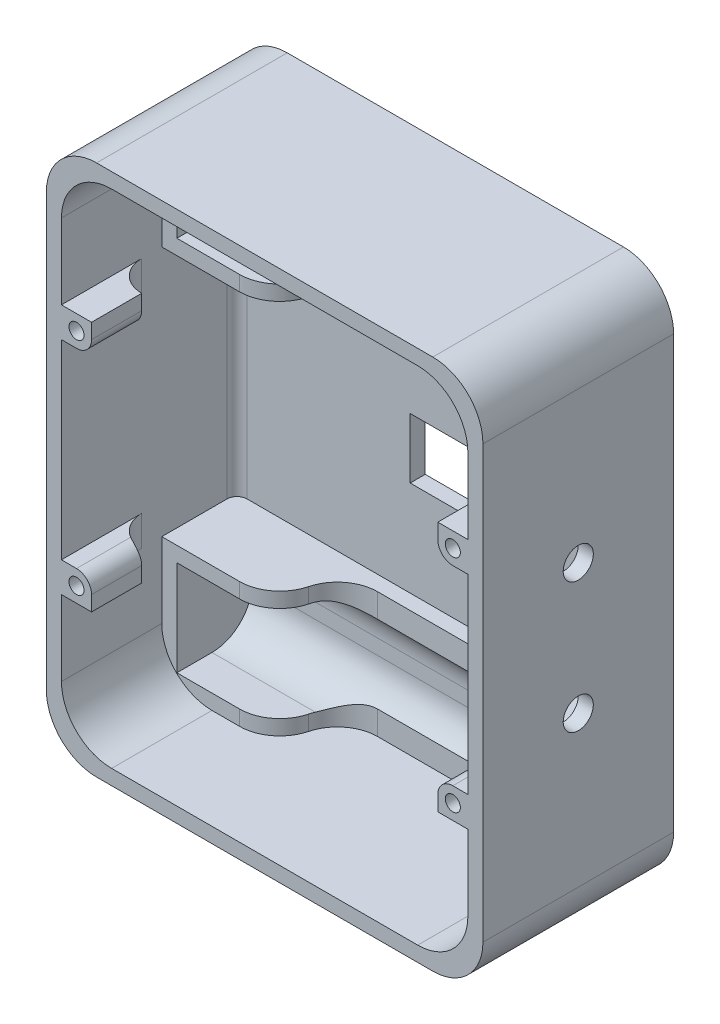
SolidWorks part; units mm, degrees
ref_plane "Front Plane" through (0, 0, 0) normal (0, 0, 1) x (1, 0, 0)
ref_plane "Top Plane" through (0, 0, 0) normal (0, 1, 0) x (1, 0, 0)
ref_plane "Right Plane" through (0, 0, 0) normal (1, 0, 0) x (0, 0, -1)
sketch "Sketch1" plane through (0, 0, 0) normal (0, 0, 1) x (1, 0, 0)
  line L0 (-3, -3) -> (78, -3)
  line L1 (0, 0) -> (75, 0)
  line L2 (0, 0) -> (0, 19)
  line L3 (0, 19) -> (75, 19)
  line L4 (75, 0) -> (75, 19)
  line L5 (78, -3) -> (78, 22)
  line L6 (-3, 22) -> (78, 22)
  line L7 (-3, -3) -> (-3, 22)
  dimension "D1" = 19
  dimension "D2" = 75
  dimension "D3" = 3
extrude "Boss-Extrude1" add sketch "Sketch1" along normal blind 18
sketch "Sketch2" plane through (0, 0, 18) normal (0, 0, 1) x (1, 0, 0)
  line L0 (75, 0) -> (75, 19) construction
  line L1 (20, 29.533) -> (55, 29.533)
  line L2 (20, 29.533) -> (20, -14.7246)
  line L3 (20, -14.7246) -> (55, -14.7246)
  line L4 (55, 29.533) -> (55, -14.7246)
  line L5 (0, 19) -> (0, 0) construction
  dimension "D1" = 20
  dimension "D2" = 20
extrude "Cut-Extrude1" cut sketch "Sketch2" against normal blind 12
sketch "Sketch3" plane through (0, 0, 0) normal (0, 0, -1) x (-1, 0, 0)
  line L1 (3, -3) -> (-78, -3)
  line L2 (3, -3) -> (3, 22)
  line L3 (3, 22) -> (-78, 22)
  line L4 (-78, -3) -> (-78, 22)
extrude "Boss-Extrude2" add sketch "Sketch3" against normal blind 3
fillet "Fillet1" radius 8 2 edges at (37.5, 0, 3) (37.5, 19, 3)
fillet "Fillet2" radius 8 4 edges at (55, 19.6225, 6) (55, -0.6225, 6) (20, -0.6225, 6) (20, 19.6225, 6)
fillet "Fillet3" radius 8 4 edges at (55, 20.5, 18) (20, 20.5, 18) (55, -1.5, 18) (20, -1.5, 18)
sketch "Sketch4" plane through (0, -3, 0) normal (0, -1, 0) x (1, 0, 0)
  line L1 (-3, 0) -> (-33, 0)
  line L2 (-3, 0) -> (-3, 3)
  line L3 (-3, 3) -> (-33, 3)
  line L4 (-33, 0) -> (-33, 3)
  dimension "D1" = 30
  dimension "D2" = 3
extrude "Boss-Extrude3" add sketch "Sketch4" against normal up to surface (25 mm away) up to face at (37.5, 22, 10.8)
sketch "Sketch5" plane through (0, -3, 0) normal (0, -1, 0) x (1, 0, 0)
  line L1 (-3, 3) -> (78, 3)
  line L2 (-3, 3) -> (-3, 0)
  line L3 (-3, 0) -> (78, 0)
  line L4 (78, 3) -> (78, 0)
extrude "Boss-Extrude4" add sketch "Sketch5" along normal blind 25
mirror "Mirror1" about plane through (0, -28, 0) normal (0, -1, 0) of bodies 105
sketch "Sketch6" plane through (0, 0, 3) normal (0, 0, 1) x (1, 0, 0)
  line L0 (-6, -81) -> (-6, 25)
  line L1 (-3, -78) -> (78, -78)
  line L2 (-3, -78) -> (-3, 22)
  line L3 (-3, 22) -> (78, 22)
  line L4 (78, -78) -> (78, 22)
  line L5 (-6, 25) -> (81, 25)
  line L6 (81, -81) -> (81, 25)
  line L7 (-6, -81) -> (81, -81)
  dimension "D1" = 3
extrude "Boss-Extrude6" add sketch "Sketch6" along normal blind 35 and the other way blind 3
sketch "Sketch7" plane through (0, 0, 3) normal (0, 0, 1) x (1, 0, 0)
  line L1 (-6, -81) -> (-52.2418, -81)
  line L2 (-6, -81) -> (-6, 49.2118)
  line L3 (-6, 49.2118) -> (-52.2418, 49.2118)
  line L4 (-52.2418, -81) -> (-52.2418, 49.2118)
extrude "Cut-Extrude2" cut sketch "Sketch7" against normal blind 35
sketch "Sketch8" plane through (0, 0, 3) normal (0, 0, 1) x (1, 0, 0)
  line L0 (-3, 22) -> (-3, -78) construction
  line L1 (31.5, -34) -> (43.5, -34)
  line L2 (31.5, -34) -> (31.5, -22)
  line L3 (31.5, -22) -> (43.5, -22)
  line L4 (43.5, -34) -> (43.5, -22)
  line L5 (28, -73.245) -> (47, -73.245) construction
  point P4 (31.5, -28)
  point P7 (-3, -28)
  point P8 (37.5, -34)
  point P11 (37.5, -73.245)
  dimension "D1" = 12
  dimension "D2" = 12
extrude "Cut-Extrude3" cut sketch "Sketch8" against normal blind 35
sketch "Sketch10" plane through (81, 0, 0) normal (1, 0, 0) x (0, 0, -1)
  line L0 (0, -81) -> (-38, -81) construction
  line L1 (0, 25) -> (-38, 25) construction
  circle A0 centre (-19, -41) radius 3
  circle A1 centre (-19, -15) radius 3
  point P7 (-19, -81)
  point P11 (-19, 25)
  dimension "D1" = 6
  dimension "D2" = 6
  dimension "D3" = 40
  dimension "D4" = 40
extrude "Cut-Extrude4" cut sketch "Sketch10" against normal blind 12
sketch "Sketch11" plane through (0, 0, 38) normal (0, 0, 1) x (1, 0, 0)
  line L0 (-3, -53) -> (-3, -3) construction
  line L1 (-3, -9) -> (0, -9)
  line L2 (-3, -9) -> (-3, -3)
  line L3 (-3, -3) -> (3, -3)
  line L4 (3, -6) -> (3, -3)
  line L6 (-3, -3) -> (12.5081, -3) construction
  line L11 (3, -50) -> (3, -53)
  line L12 (-3, -53) -> (3, -53)
  line L13 (-3, -47) -> (-3, -53)
  line L14 (-3, -47) -> (0, -47)
  line L15 (78, -47) -> (75, -47)
  line L16 (78, -47) -> (78, -53)
  line L17 (78, -53) -> (72, -53)
  line L18 (72, -50) -> (72, -53)
  line L19 (72, -6) -> (72, -3)
  line L20 (78, -3) -> (72, -3)
  line L21 (78, -9) -> (78, -3)
  line L22 (78, -9) -> (75, -9)
  circle A0 centre (0, -6) radius 1.5
  arc A5 (0, -9) -> (3, -6) centre (0, -6) ccw
  arc A6 (0, -47) -> (3, -50) centre (0, -50) cw
  circle A7 centre (0, -50) radius 1.5
  circle A8 centre (75, -50) radius 1.5
  arc A9 (75, -47) -> (72, -50) centre (75, -50) ccw
  arc A10 (75, -9) -> (72, -6) centre (75, -6) cw
  circle A11 centre (75, -6) radius 1.5
  point P9 (3, -6)
  point P11 (0, -9)
  dimension "D1" = 3
extrude "Boss-Extrude8" add sketch "Sketch11" against normal blind 10
fillet "Fillet4" radius 6 4 edges at (78, -6, 28) (78, -50, 28) (-3, -50, 28) (-3, -6, 28)
fillet "Fillet5" radius 10 8 edges at (-6, -81, 19) (81, -81, 19) (81, 25, 19) (-6, 25, 19) (-3, -78, 28) (-3, 22, 28) (78, -78, 28) (78, 22, 28)
fillet "Fillet6" radius 2 2 edges at (-3, -28, 3) (78, -28, 3)
